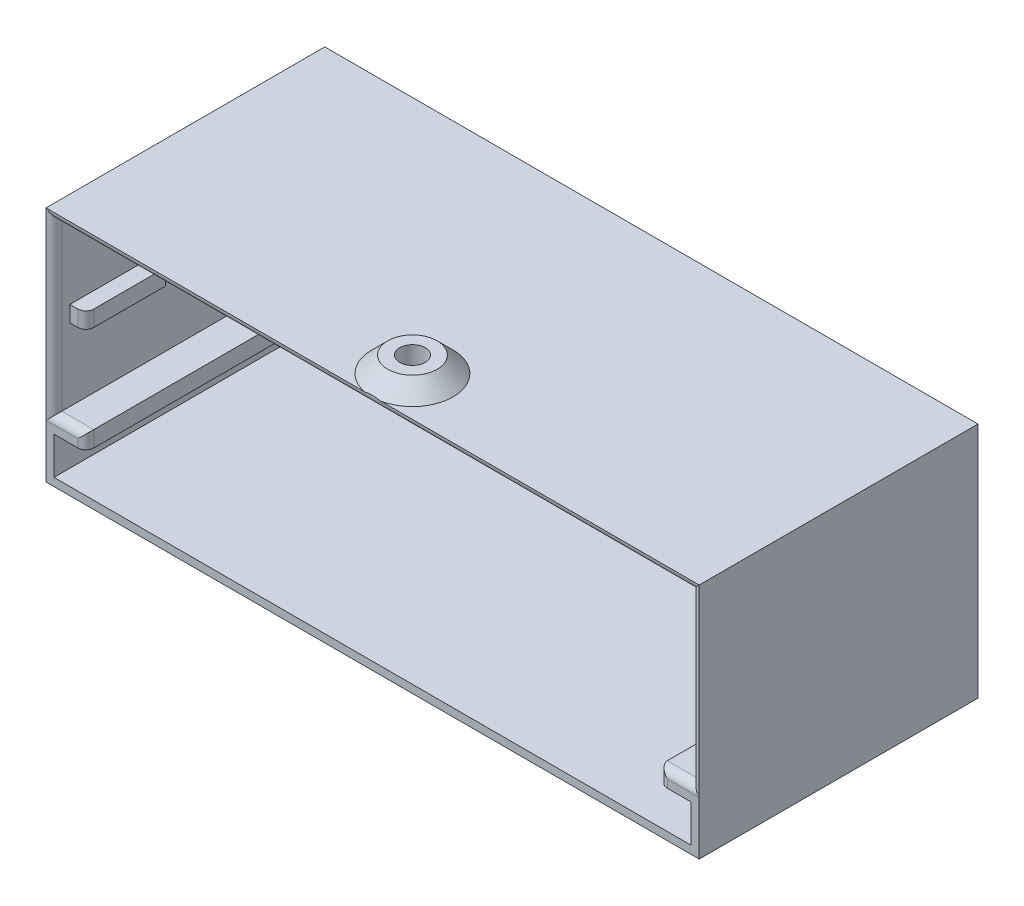
SolidWorks part; units mm, degrees
ref_plane "Front Plane" through (0, 0, 0) normal (0, 0, 1) x (1, 0, 0)
ref_plane "Top Plane" through (0, 0, 0) normal (0, 1, 0) x (1, 0, 0)
ref_plane "Right Plane" through (0, 0, 0) normal (1, 0, 0) x (0, 0, -1)
sketch "Sketch1" plane through (0, 0, 0) normal (0, 0, 1) x (1, 0, 0)
  line L1 (41, -14.9) -> (-41, -14.9)
  line L2 (41, -14.9) -> (41, 14.9)
  line L3 (41, 14.9) -> (-41, 14.9)
  line L4 (-41, -14.9) -> (-41, 14.9)
  line L5 (41, -14.9) -> (-41, 14.9) construction
  line L6 (41, 14.9) -> (-41, -14.9) construction
  point P0 (0, 0)
  dimension "D1" = 29.8
  dimension "D2" = 82
extrude "Boss-Extrude1" add sketch "Sketch1" along normal blind 3
sketch "Sketch2" plane through (0, 0, 3) normal (0, 0, 1) x (1, 0, 0)
  line L1 (41, -14.9) -> (-41, -14.9)
  line L2 (41, -14.9) -> (41, 14.9)
  line L3 (41, 14.9) -> (-41, 14.9)
  line L4 (-41, -14.9) -> (-41, 14.9)
  line L5 (41, -14.9) -> (-41, 14.9) construction
  line L6 (41, 14.9) -> (-41, -14.9) construction
  line L7 (40, -13.9) -> (-40, -13.9)
  line L8 (40, -13.9) -> (40, 13.9)
  line L9 (40, 13.9) -> (-40, 13.9)
  line L10 (-40, -13.9) -> (-40, 13.9)
  line L11 (40, -13.9) -> (-40, 13.9) construction
  line L12 (40, 13.9) -> (-40, -13.9) construction
  point P0 (0, 0)
  point P7 (0, 0)
  dimension "D1" = 1
  dimension "D2" = 1
extrude "Boss-Extrude2" add sketch "Sketch2" along normal blind 32
sketch "Sketch3" plane through (0, 0, 3) normal (0, 0, 1) x (1, 0, 0)
  line L0 (-40, 13.9) -> (-40, -13.9) construction
  line L1 (-40, -7.2) -> (-36, -7.2)
  line L2 (-40, -7.2) -> (-40, -9.2)
  line L3 (-40, -9.2) -> (-36, -9.2)
  line L4 (-36, -7.2) -> (-36, -9.2)
  line L5 (40, -13.9) -> (40, 13.9) construction
  line L6 (40, -7.2) -> (36, -7.2)
  line L7 (40, -7.2) -> (40, -9.2)
  line L8 (40, -9.2) -> (36, -9.2)
  line L9 (36, -7.2) -> (36, -9.2)
  line L10 (40, 13.9) -> (-40, 13.9) construction
  line L11 (40, 13.9) -> (-40, 13.9) construction
  dimension "D1" = 2
  dimension "D2" = 2
  dimension "D3" = 4
  dimension "D4" = 4
  dimension "D5" = 21.1
  dimension "D6" = 21.1
extrude "Boss-Extrude3" add sketch "Sketch3" along normal up to surface (32 mm away) from offset 5 up to face at (0, 0, 35)
sketch "Sketch11" plane through (0, 14.9, 0) normal (0, 1, 0) x (1, 0, 0)
  line L0 (41, -35) -> (-41, -35) construction
  line L1 (-41, -35) -> (-41, 0) construction
  circle A0 centre (0, -30) radius 1.6
  dimension "D1" = 5
  dimension "D2" = 41
  dimension "D3" = 3.2
extrude "Cut-Extrude5" cut sketch "Sketch11" against normal up to surface (1 mm away) contours A0 up to face at (0, 13.9, 19)
sketch "Sketch13" plane through (0, 0, 0) normal (0, 0, -1) x (-1, 0, 0)
  line L0 (41, -14.9) -> (-41, -14.9) construction
  line L1 (-39, -6.9) -> (-30, -6.9)
  line L2 (-39, -6.9) -> (-39, -12.9)
  line L3 (-39, -12.9) -> (-30, -12.9)
  line L4 (-30, -6.9) -> (-30, -12.9)
  line L5 (-41, -14.9) -> (-41, 14.9) construction
  line L6 (-41, 14.9) -> (41, 14.9) construction
  line L7 (41, 14.9) -> (41, -14.9) construction
  circle A0 centre (0, 3.35) radius 1.75
  circle A1 centre (0, -10.65) radius 1.75
  dimension "D5" = 11.55
  dimension "D6" = 3.5
  dimension "D7" = 14
  dimension "D8" = 41
  dimension "D9" = 41
  dimension "D1" = 6
  dimension "D2" = 9
  dimension "D3" = 2
  dimension "D4" = 2
extrude "Cut-Extrude6" cut sketch "Sketch13" against normal up to surface (3 mm away) up to face at (0, 0, 3)
chamfer "Chamfer1" distance 5 angle 45 1 edges at (36, -8.2, 8)
sketch "Sketch14" plane through (0, 0, 3) normal (0, 0, 1) x (1, 0, 0)
  line L0 (-40, 13.9) -> (-40, -7.2) construction
  line L1 (-40, 3.9) -> (-38, 3.9)
  line L2 (-40, 3.9) -> (-40, 1.9)
  line L3 (-40, 1.9) -> (-38, 1.9)
  line L4 (-38, 3.9) -> (-38, 1.9)
  line L5 (40, -7.2) -> (40, 13.9) construction
  line L6 (40, 3.9) -> (38, 3.9)
  line L7 (40, 3.9) -> (40, 1.9)
  line L8 (40, 1.9) -> (38, 1.9)
  line L9 (38, 3.9) -> (38, 1.9)
  line L10 (40, 13.9) -> (-40, 13.9) construction
  line L11 (40, 13.9) -> (-40, 13.9) construction
  dimension "D1" = 2
  dimension "D2" = 2
  dimension "D3" = 2
  dimension "D4" = 2
  dimension "D5" = 10
  dimension "D6" = 10
extrude "Boss-Extrude4" add sketch "Sketch14" along normal blind 10 from offset 20
fillet "Fillet1" radius 1 9 edges at (-36, -8.2, 35) (-38, -7.2, 35) (-40, 3.35, 35) (0, 13.9, 35) (38, 2.9, 33) (38, -7.2, 35) (40, 3.35, 35) (36, -8.2, 35) (-38, 2.9, 33)
sketch "Sketch15" plane through (0, 14.9, 0) normal (0, 1, 0) x (1, 0, 0)
  circle A0 centre (0, -30) radius 1.6
  circle A1 centre (0, -30) radius 3.1
  circle A2 centre (0, -30) radius 1.6 construction
  dimension "D1" = 1.5
extrude "Boss-Extrude5" add sketch "Sketch15" along normal blind 2
chamfer "Chamfer2" distance 2 angle 45 1 edges at (3.1, 14.9, 30)
chamfer "Chamfer3" distance 2 angle 45 2 edges at (-40, 2.9, 23) (40, 2.9, 23)
sketch "Sketch16" plane through (0, 0, 3) normal (0, 0, 1) x (1, 0, 0)
  line L0 (-40, 13.9) -> (-40, -13.9) construction
  line L1 (-40, 13.9) -> (40, 13.9)
  line L2 (-40, 13.9) -> (-40, -13.9)
  line L3 (-40, -13.9) -> (40, -13.9)
  line L4 (40, 13.9) -> (40, -13.9)
  line L5 (40, 13.9) -> (-40, 13.9) construction
  line L6 (-40, -13.9) -> (40, -13.9) construction
  line L7 (40, -13.9) -> (40, 13.9) construction
extrude "Cut-Extrude7" cut sketch "Sketch16" against normal blind 1.5
